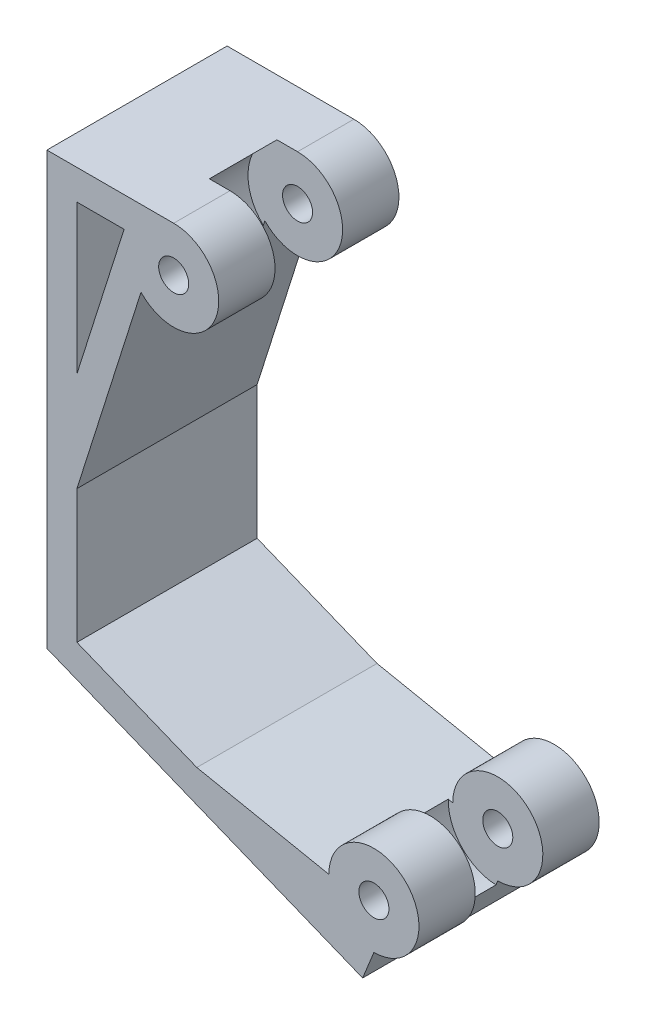
SolidWorks part; units mm, degrees
other "Markup1"
sketch "Sketch3" plane through (0, 0, 12) normal (0, 0, 1) x (1, 0, 0)
other "DetailItem1"
other "DetailItem3"
other "DetailItem5"
ref_plane "Front Plane" through (0, 0, 0) normal (0, 0, 1) x (1, 0, 0)
ref_plane "Top Plane" through (0, 0, 0) normal (0, 1, 0) x (1, 0, 0)
ref_plane "Right Plane" through (0, 0, 0) normal (1, 0, 0) x (0, 0, -1)
sketch "Sketch1" plane through (0, 0, 0) normal (0, 0, 1) x (1, 0, 0)
  line L2 (0, 6.6822) -> (0, 35.4227)
  line L3 (0, 35.4227) -> (8.4433, 35.4227)
  line L5 (6.2674, 30.3574) -> (2, 16.8962)
  line L6 (2, 16.8962) -> (2, 8.0313)
  line L7 (9.9848, 4.8052) -> (18.7771, 3.0408)
  line L11 (8.4433, 32.4227) -> (21.7771, 3.0408) construction
  line L12 (5.141, 33.4227) -> (2, 33.4227)
  line L13 (2, 33.4227) -> (2, 23.5145)
  line L14 (2, 23.5145) -> (5.141, 33.4227)
  line L15 (8.4433, 32.4227) -> (8.4433, 5.1527) construction
  line L16 (8.4433, 5.1527) -> (21.7771, 3.0408) construction
  line L17 (8.4433, 5.1527) -> (8.4433, -11.7713) construction
  line L21 (2, 8.0313) -> (9.9848, 4.8052)
  line L22 (-988.9008, 0.0408) -> (16.4382, 0.0408) construction
  line L23 (0, 6.6822) -> (21.0279, -1.8136)
  line L24 (-906.156, 372.793) -> (46380.2206, -18732.1432) construction
  line L25 (21.7771, 0.0408) -> (50021.7771, 0.0408) construction
  line L26 (21.7771, 0.0408) -> (21.0279, -1.8136)
  line L27 (-905.4067, 374.6474) -> (46380.9698, -18730.2889) construction
  arc A0 (21.7771, 0.0408) -> (18.7771, 3.0408) centre (21.7771, 3.0408) ccw
  arc A1 (8.4433, 35.4227) -> (6.2674, 30.3574) centre (8.4433, 32.4227) cw
  circle A2 centre (8.4433, 32.4227) radius 1
  circle A3 centre (21.7771, 3.0408) radius 1
  dimension "D1" = 2
  dimension "D3" = 3
  dimension "D6" = 2
  dimension "D4" = 27.27
  dimension "D5" = 13.5
  dimension "D8" = 81
  dimension "D11" = 2
  dimension "D7" = 2
  dimension "D12" = 22
  dimension "D2" = 2
  dimension "D13" = 2
extrude "Boss-Extrude1" add sketch "Sketch1" along normal blind 12
ref_plane "midplane" through (0, 0, 6) normal (0, 0, 1) x (1, 0, 0)
sketch "Sketch2" plane through (0, 0, 6) normal (0, 0, 1) x (1, 0, 0)
  circle A0 centre (8.4433, 32.4227) radius 3.3
  circle A1 centre (21.7771, 3.0408) radius 3.3
  dimension "D1" = 6.6
extrude "Cut-Extrude1" cut sketch "Sketch2" against normal blind 2.25 and the other way blind 2.25
equation "\"axle-diameter\"=2"
equation "\"D1@Sketch1\"=\"axle-diameter\""
equation "\"switch-thickness\"=12"
equation "\"D1@Boss-Extrude1\"=\"switch-thickness\""
equation "\"base-width\"=4.0"
equation "\"axle-bushing-radius\"=3"
equation "\"D3@Sketch1\"= \"axle-bushing-radius\""
equation "\"D1@Sketch2\"=\"axle-bushing-radius\"*2.2"
equation "\"D1@Cut-Extrude1\"=\"switch-thickness\"/6+\"clearance\""
equation "\"D2@Cut-Extrude1\"=\"switch-thickness\"/6+\"clearance\""
equation "\"clearance\"= 0.25"
equation "\"arm-width\"=3.0"
equation "\"min-diameter\"=70"
